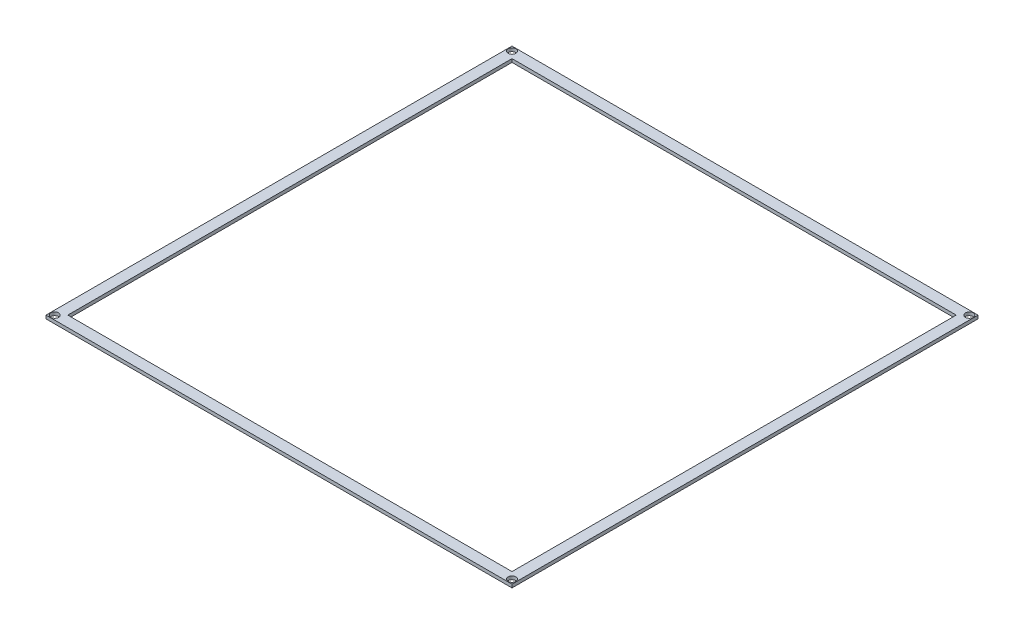
SolidWorks part; units mm, degrees
ref_plane "Front Plane" through (0, 0, 0) normal (0, 0, 1) x (1, 0, 0)
ref_plane "Top Plane" through (0, 0, 0) normal (0, 1, 0) x (1, 0, 0)
ref_plane "Right Plane" through (0, 0, 0) normal (1, 0, 0) x (0, 0, -1)
sketch "Sketch1" plane through (0, 0, 0) normal (0, 1, 0) x (1, 0, 0)
  line L1 (107, 107) -> (-107, 107)
  line L2 (107, 107) -> (107, -107)
  line L3 (107, -107) -> (-107, -107)
  line L4 (-107, 107) -> (-107, -107)
  line L5 (0, -107) -> (0, 107) construction
  line L6 (107, 0) -> (-107, 0) construction
  point P0 (0, 0)
  dimension "D1" = 214
  dimension "D2" = 214
extrude "Boss-Extrude1" add sketch "Sketch1" along normal blind 1.5189
sketch "Sketch2" plane through (0, 1.5189, 0) normal (0, 1, 0) x (1, 0, 0)
  line L0 (107, 107) -> (-107, 107) construction
  line L1 (-102, -102) -> (102, -102)
  line L2 (-102, -102) -> (-102, 102)
  line L3 (-102, 102) -> (102, 102)
  line L4 (102, -102) -> (102, 102)
  line L5 (0, 102) -> (0, -102) construction
  line L6 (-102, 0) -> (102, 0) construction
  line L7 (107, -107) -> (107, 107) construction
  point P0 (0, 0)
  dimension "D1" = 5
  dimension "D2" = 5
extrude "Cut-Extrude1" cut sketch "Sketch2" against normal blind 1.5189
hole_wizard "M3 Clearance Hole1" positions "Sketch5" profile "Sketch4" hole size "M3" standard "ANSI Metric" end condition through all
sketch "Sketch5" plane through (0, 1.5189, 0) normal (0, 1, 0) x (1, 0, 0)
  line L1 (-105, -105) -> (105, -105)
  line L2 (-105, -105) -> (-105, 105)
  line L3 (-105, 105) -> (105, 105)
  line L4 (105, -105) -> (105, 105)
  line L5 (-107, 107) -> (-107, -107) construction
  line L6 (107, 107) -> (-107, 107) construction
  point P0 (-105, 105)
  point P2 (105, 105)
  point P4 (105, -105)
  point P6 (-105, -105)
  dimension "D1" = 210
  dimension "D2" = 210
  dimension "D3" = 2
  dimension "D4" = 2
sketch "Sketch4" plane through (-105, 1.5189, -105) normal (1, 0, 0) x (0, 0, 1)
  line L0 (0, 0) -> (0, 1.5189)
  line L1 (0, 1.5189) -> (1.8, 1.5189)
  line L2 (1.8, 1.5189) -> (1.8, 0)
  line L5 (1.8, 0) -> (0, 0)
  line L11 (0, -6.35) -> (0, 107.95) construction
  dimension "Thru Hole Dia." = 3.6
  dimension "Thru Hole Depth" = 1.5189
